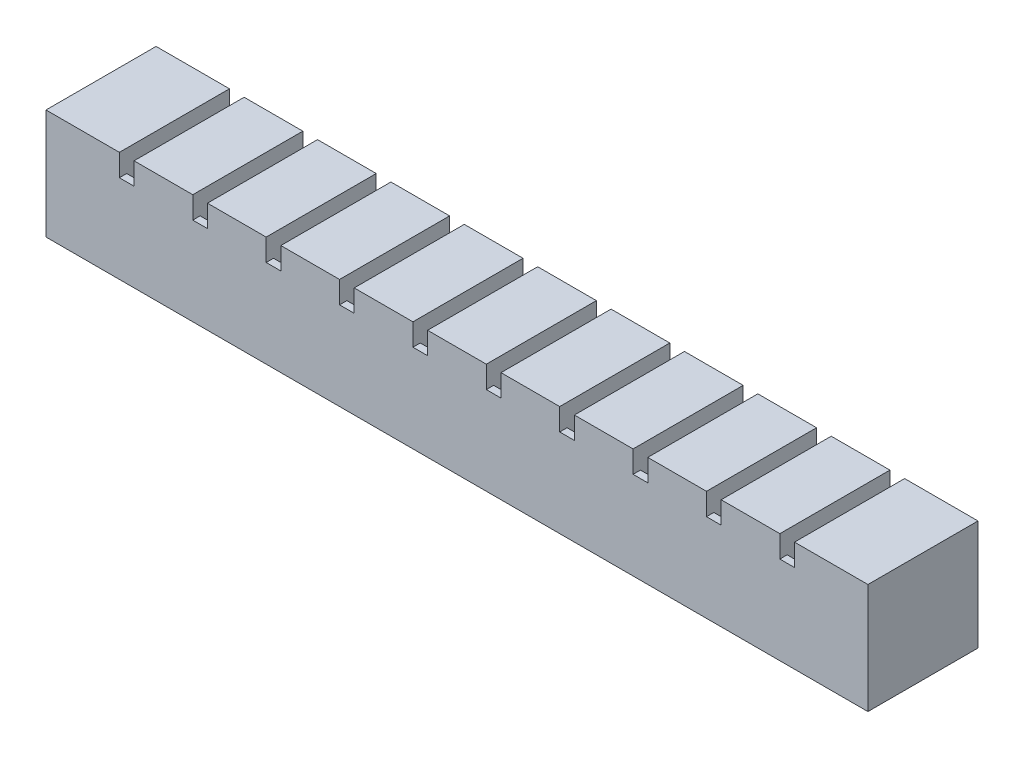
SolidWorks part; units mm, degrees
ref_plane "Front Plane" through (0, 0, 0) normal (0, 0, 1) x (1, 0, 0)
ref_plane "Top Plane" through (0, 0, 0) normal (0, 1, 0) x (1, 0, 0)
ref_plane "Right Plane" through (0, 0, 0) normal (1, 0, 0) x (0, 0, -1)
sketch "Sketch1" plane through (0, 0, 0) normal (0, 0, 1) x (1, 0, 0)
  line L1 (0, 0) -> (8, 0)
  line L2 (0, 0) -> (0, 15)
  line L3 (0, 15) -> (8, 15)
  line L4 (8, 0) -> (8, 15)
  dimension "D1" = 8
  dimension "D2" = 15
extrude "first chamber block" add sketch "Sketch1" along normal blind 15
sketch "Sketch2" plane through (0, 0, 0) normal (0, -1, 0) x (1, 0, 0)
  line L0 (8, 15) -> (8, 0) construction
  line L1 (1, 13) -> (7, 13)
  line L2 (1, 13) -> (1, 2)
  line L3 (1, 2) -> (7, 2)
  line L4 (7, 13) -> (7, 2)
  line L5 (0, 15) -> (0, 0) construction
  line L6 (0, 15) -> (8, 15) construction
  line L7 (0, 0) -> (8, 0) construction
  dimension "D1" = 1
  dimension "D2" = 1
  dimension "D3" = 2
  dimension "D4" = 2
extrude "first chamber cavity" cut sketch "Sketch2" against normal blind 13
sketch "Sketch3" plane through (8, 0, 0) normal (1, 0, 0) x (0, 0, -1)
  line L0 (-15, 0) -> (-15, 15) construction
  line L1 (0, 0) -> (-15, 0)
  line L2 (0, 0) -> (0, 3)
  line L3 (0, 3) -> (-15, 3)
  line L4 (-15, 0) -> (-15, 3)
  dimension "D1" = 3
extrude "chamber spacer" add sketch "Sketch3" along normal blind 2
pattern_linear "pattern chambers" count 11 spacing 10 along (1, 0, 0) of "chamber spacer", "first chamber cavity", "first chamber block"
combine bodies "combine into 1 solid body" operation type add bodies to combine 123 122 121 120 119 118 117 116 115 114 103
sketch "Sketch4" plane through (108, 0, 0) normal (1, 0, 0) x (0, 0, -1)
  line L1 (0, 15) -> (-15, 15)
  line L2 (0, 15) -> (0, 3)
  line L3 (0, 3) -> (-15, 3)
  line L4 (-15, 15) -> (-15, 3)
extrude "thicken end 1" add sketch "Sketch4" along normal up to surface (2 mm away) up to face at (110, 1.5, 7.5)
sketch "Sketch5" plane through (0, 0, 0) normal (-1, 0, 0) x (0, 0, 1)
  line L1 (15, 15) -> (0, 15)
  line L2 (15, 15) -> (15, 0)
  line L3 (15, 0) -> (0, 0)
  line L4 (0, 15) -> (0, 0)
extrude "thicken end 2" add sketch "Sketch5" along normal blind 2
ref_point "center of bottom face"
sketch "Sketch6" plane through (0, 0, 0) normal (0, -1, 0) x (1, 0, 0)
  line L0 (7, 2) -> (7, 13) construction
  line L1 (101, 6.5) -> (7, 6.5)
  line L2 (101, 6.5) -> (101, 8.5)
  line L3 (101, 8.5) -> (7, 8.5)
  line L4 (7, 6.5) -> (7, 8.5)
  line L5 (101, 6.5) -> (7, 8.5) construction
  line L6 (101, 8.5) -> (7, 6.5) construction
  point P0 (54, 7.5)
  dimension "D1" = 2
extrude "central air channel" cut sketch "Sketch6" against normal blind 2
sketch "Sketch7" plane through (0, 0, 0) normal (0, -1, 0) x (1, 0, 0)
  line L0 (0, 14) -> (108, 14)
  line L1 (1, 13) -> (107, 13)
  line L2 (1, 13) -> (1, 2)
  line L3 (1, 2) -> (107, 2)
  line L4 (107, 13) -> (107, 2)
  line L5 (108, 14) -> (108, 1)
  line L6 (0, 1) -> (108, 1)
  line L7 (0, 14) -> (0, 1)
  dimension "D1" = 1
extrude "bonding ridge" add sketch "Sketch7" along normal blind 2
sketch "Sketch9" plane through (0, 0, 0) normal (0, -1, 0) x (1, 0, 0)
  line L0 (11, 8.5) -> (11, 13) construction
  line L1 (11, 13) -> (7, 13) construction
  line L2 (7, 13) -> (7, 8.5) construction
  line L3 (7, 8.5) -> (11, 8.5) construction
  line L4 (7, 6.5) -> (7, 2) construction
  line L5 (7, 2) -> (11, 2) construction
  line L6 (11, 2) -> (11, 6.5) construction
  line L7 (11, 6.5) -> (7, 6.5) construction
  line L8 (11, 8.5) -> (11, 13) construction
  line L9 (11, 13) -> (7, 13) construction
  line L10 (7, 13) -> (7, 8.5) construction
  line L11 (7, 8.5) -> (11, 8.5) construction
  line L12 (7, 6.5) -> (7, 2) construction
  line L13 (7, 2) -> (11, 2) construction
  line L14 (11, 2) -> (11, 6.5) construction
  line L15 (11, 6.5) -> (7, 6.5) construction
  line L16 (10, 9.5) -> (10, 12)
  line L17 (10, 12) -> (8, 12)
  line L18 (8, 12) -> (8, 9.5)
  line L19 (8, 9.5) -> (10, 9.5)
  line L20 (8, 5.5) -> (8, 3)
  line L21 (8, 3) -> (10, 3)
  line L22 (10, 3) -> (10, 5.5)
  line L23 (10, 5.5) -> (8, 5.5)
  dimension "D1" = 1
extrude "bonding bumps" add sketch "Sketch9" along normal blind 2
pattern_linear "pattern bonding bumps" count 10 spacing 10 along (1, 0, 0) of "bonding bumps"
sketch "Skizze1" plane through (0, 0, 0) normal (0, -1, 0) x (1, 0, 0)
  line L4 (-2, 0) -> (110, 0)
  line L5 (110, 0) -> (110, 15)
  line L6 (110, 15) -> (-2, 15)
  line L7 (-2, 15) -> (-2, 0)
  line L8 (-2, 0) -> (110, 0)
  line L9 (110, 0) -> (110, 15)
  line L10 (110, 15) -> (-2, 15)
  line L11 (-2, 15) -> (-2, 0)
  dimension "D1" = 0
extrude "Schnitt-Linear austragen1" cut sketch "Skizze1" along normal through all
sketch "Skizze2" plane through (0, 3, 0) normal (0, 1, 0) x (1, 0, 0)
  line L0 (98, 0) -> (98, -15) construction
  line L1 (100, 0) -> (98, 0)
  line L2 (100, 0) -> (100, -1)
  line L3 (100, -1) -> (98, -1)
  line L4 (98, 0) -> (98, -1)
  line L5 (100, 0) -> (100, -15) construction
  line L6 (98, -15) -> (100, -15)
  line L7 (98, -15) -> (98, -14)
  line L8 (98, -14) -> (100, -14)
  line L9 (100, -15) -> (100, -14)
  dimension "D1" = 1
extrude "Aufsatz-Linear austragen1" add sketch "Skizze2" along normal offset from surface (9 mm away) 3 up to face at (105, 15, 7.5)
pattern_linear "Lineares Muster1" count 10 spacing 10 along (-1, 0, 0) of "Aufsatz-Linear austragen1"
sketch "Skizze3" plane through (0, 0, 2) normal (0, 0, 1) x (1, 0, 0)
  line L0 (104, 0) -> (104, 13) construction
  line L1 (107, 0) -> (101, 0) construction
  line L2 (101, 13) -> (107, 13) construction
  circle A0 centre (104, 6.8582) radius 1.25
  dimension "D1" = 2.5
extrude "Schnitt-Linear austragen2" [suppressed] cut sketch "Skizze3" along normal through all
sketch "Skizze4" plane through (0, 0, 2) normal (0, 0, 1) x (1, 0, 0)
  line L0 (4, 13) -> (4, 0) construction
  line L1 (1, 13) -> (7, 13) construction
  line L2 (7, 0) -> (1, 0) construction
  circle A0 centre (4, 6.5) radius 1.25
  dimension "D1" = 2.5
extrude "Schnitt-Linear austragen3" cut sketch "Skizze4" against normal through all
